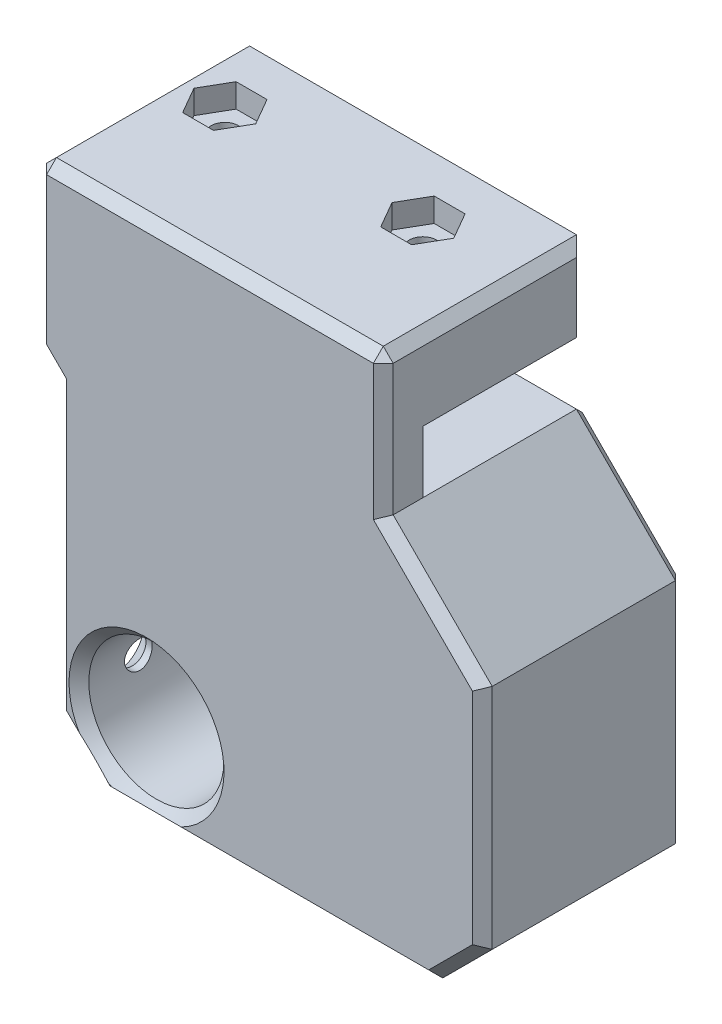
SolidWorks part; units mm, degrees
note: The reader was unsure of these and kept them because the rebuilt part matched: shared geometry of "스케치10<3>".
ref_plane "정면" through (0, 0, 0) normal (0, 0, 1) x (1, 0, 0)
ref_plane "윗면" through (0, 0, 0) normal (0, 1, 0) x (1, 0, 0)
ref_plane "우측면" through (0, 0, 0) normal (1, 0, 0) x (0, 0, -1)
sketch "스케치1" plane through (0, 0, 0) normal (0, 0, 1) x (1, 0, 0)
  line L0 (0, 0) -> (0, -2)
  line L1 (0, -2) -> (2, -4)
  line L2 (2, -4) -> (2, -33)
  line L3 (2, -33) -> (7, -38)
  line L4 (7, -38) -> (40, -38)
  line L5 (40, -38) -> (45, -33)
  line L6 (45, -33) -> (45, -10)
  line L7 (45, -10) -> (35, 0)
  line L8 (35, 0) -> (0, 0)
  dimension "D1" = 35
  dimension "D2" = 10
  dimension "D3" = 2
  dimension "D4" = 5
  dimension "D5" = 5
  dimension "D6" = 38
  dimension "D7" = 2
  dimension "D8" = 2
extrude "보스-돌출1" add sketch "스케치1" against normal blind 5
sketch "스케치2" plane through (0, 0, 0) normal (0, 0, 1) x (1, 0, 0)
  line L0 (0, -2) -> (0, 14.25)
  line L1 (0, 14.25) -> (35, 14.25)
  line L2 (35, 14.25) -> (35, -4)
  line L3 (35, -4) -> (2, -4)
  line L4 (2, -4) -> (0, -2)
  line L5 (0, 6.25) -> (35, 6.25) construction
  line L6 (35, 0) -> (0, 0) construction
  line L7 (2, -4) -> (2, -33) construction
  line L8 (7, -38) -> (40, -38) construction
  line L9 (45, -33) -> (45, -10) construction
  dimension "D1" = 6.25
  dimension "D2" = 8
extrude "보스-돌출2" add sketch "스케치2" along normal blind 4
sketch "스케치3" plane through (0, 0, 0) normal (0, 0, -1) x (-1, 0, 0)
  line L0 (-35, 0) -> (-35, 14.25) construction
  line L1 (0, 14.25) -> (-35, 14.25)
  line L2 (0, 14.25) -> (0, 6.25)
  line L3 (0, 6.25) -> (-35, 6.25)
  line L4 (-35, 14.25) -> (-35, 6.25)
  dimension "D1" = 8
sketch "스케치4" plane through (0, 0, 0) normal (0, 1, 0) x (1, 0, 0)
  line L2 (35, 0) -> (25, 0) construction
  line L3 (35, 0) -> (35, 10) construction
  line L4 (35, 10) -> (25, 10) construction
  line L5 (25, 0) -> (25, 10) construction
  dimension "D1" = 10
  dimension "D2" = 10
extrude "보스-돌출3" add sketch "스케치3" along normal blind 16.5 contours L3 L4 L1 L2
sketch "스케치5" plane through (0, 0, -5) normal (0, 0, -1) x (-1, 0, 0)
  line L0 (-35, -11.75) -> (-35, -38)
  line L1 (-35, -11.75) -> (-32, -8.75)
  line L2 (-2, -4) -> (0, -2)
  line L3 (-7, -38) -> (-40, -38) construction
  line L4 (-35, -38) -> (-40, -38)
  line L5 (-40, -38) -> (-45, -33)
  line L6 (-45, -33) -> (-45, -10)
  line L7 (-45, -10) -> (-35, 0)
  line L8 (-35, 0) -> (0, 0)
  line L9 (0, 0) -> (0, -2)
  line L10 (-2, -4) -> (-2, -8.75)
  line L11 (-2, -4) -> (-2, -33) construction
  line L12 (-2, -8.75) -> (-32, -8.75)
  line L15 (0, 14.25) -> (-35, 14.25) construction
  point P28 (-32.5508, -8.6209)
  dimension "D1" = 23
  dimension "D2" = 10
  dimension "D3" = 3
  dimension "D4" = 3
extrude "보스-돌출4" add sketch "스케치5" along normal blind 11.5
sketch "스케치6" plane through (0, 0, 0) normal (0, 1, 0) x (1, 0, 0)
  line L0 (5, 10) -> (25, 10) construction
  circle A0 centre (25, 10) radius 1.375
  circle A1 centre (5, 10) radius 1.375
  dimension "D2" = 2.75
  dimension "D3" = 2.75
  dimension "D1" = 20
extrude "컷-돌출1" cut sketch "스케치6" against normal through all both and the other way through all
sketch "스케치7" plane through (0, 14.25, 0) normal (0, 1, 0) x (1, 0, 0)
  line L1 (8.1177, 10) -> (6.5588, 12.7)
  line L2 (6.5588, 12.7) -> (3.4412, 12.7)
  line L3 (3.4412, 12.7) -> (1.8823, 10)
  line L4 (1.8823, 10) -> (3.4412, 7.3)
  line L5 (3.4412, 7.3) -> (6.5588, 7.3)
  line L6 (6.5588, 7.3) -> (8.1177, 10)
  line L7 (28.1177, 10) -> (26.5588, 12.7)
  line L8 (26.5588, 12.7) -> (23.4412, 12.7)
  line L9 (23.4412, 12.7) -> (21.8823, 10)
  line L10 (21.8823, 10) -> (23.4412, 7.3)
  line L11 (23.4412, 7.3) -> (26.5588, 7.3)
  line L12 (26.5588, 7.3) -> (28.1177, 10)
  circle A0 centre (5, 10) radius 2.7 construction
  circle A1 centre (25, 10) radius 2.7 construction
  dimension "D1" = 5.4
  dimension "D2" = 5.4
extrude "컷-돌출2" cut sketch "스케치7" against normal blind 2.4
sketch "스케치9" plane through (0, -8.75, 0) normal (0, -1, 0) x (1, 0, 0)
  circle A0 centre (5, -10) radius 2.7
  circle A1 centre (25, -10) radius 2.7
  dimension "D1" = 5.4
  dimension "D2" = 5.4
extrude "컷-돌출4" cut sketch "스케치9" against normal blind 3
sketch "스케치10" plane through (0, 0, -5) normal (0, 0, -1) x (-1, 0, 0)
  line L0 (-11.092, -30) -> (-27.592, -30) construction
  line L1 (-27.592, -22.8002) -> (-35, -22.8002)
  line L2 (-35, -38) -> (-35, -11.75) construction
  line L3 (-35, -22.8002) -> (-35, -38)
  line L4 (-7, -38) -> (-35, -38) construction
  line L5 (-20.3923, -31.5) -> (-20.3923, -38)
  line L6 (-20.3923, -38) -> (-35, -38)
  line L7 (-23.83, -28.5) -> (-20.5502, -28.5)
  line L8 (-23.83, -31.5) -> (-20.3923, -31.5)
  line L9 (-23.83, -31.5) -> (-23.83, -28.5)
  line L10 (-18.842, -30) -> (-18.842, -38)
  line L11 (-18.842, -38) -> (-7, -38)
  line L12 (-7, -38) -> (-2, -33)
  line L13 (-2, -33) -> (-2, -22.25)
  line L14 (-2, -8.75) -> (-2, -33) construction
  line L15 (-2, -22.25) -> (-11.092, -22.25)
  circle A0 centre (-11.092, -30) radius 4.5
  arc A1 (-23.83, -28.5) -> (-23.83, -31.5) centre (-27.592, -30) ccw
  arc A2 (-20.5502, -28.5) -> (-27.592, -22.8002) centre (-27.592, -30) ccw
  arc A3 (-11.092, -22.25) -> (-18.842, -30) centre (-11.092, -30) ccw
  point P19 (-23.83, -30)
  dimension "D1" = 8.1
  dimension "D3" = 9
  dimension "D6" = 15.5
  dimension "D2" = 16.5
  dimension "D4" = 8
  dimension "D5" = 3
extrude "보스-돌출5" add sketch "스케치10" along normal blind 5
extrude "보스-돌출6" add sketch "스케치10<3>" along normal blind 10
sketch "스케치10<3>" plane through (0, 0, -5) normal (0, 0, -1) x (-1, 0, 0) same geometry as "스케치10"
sketch "스케치13" plane through (0, 0, 0) normal (0, 0, 1) x (1, 0, 0)
  circle A0 centre (11.092, -30) radius 6.825
  dimension "D1" = 13.65
extrude "컷-돌출5" cut sketch "스케치13" against normal blind 8
sketch "스케치14" plane through (0, 0, -8) normal (0, 0, 1) x (1, 0, 0)
  circle A0 centre (11.092, -30) radius 6.025
  dimension "D1" = 12.05
extrude "컷-돌출6" cut sketch "스케치14" against normal blind 2.8
sketch "스케치15" plane through (2, 0, 0) normal (-1, 0, 0) x (0, 0, 1)
  line L0 (-10.8, -30) -> (2.5202, -30) construction
  line L1 (-10.8, -36.025) -> (-10.8, -23.975) construction
  line L2 (0, -4) -> (0, -33) construction
  circle A0 centre (-2, -30) radius 1.4
  dimension "D1" = 2.8
  dimension "D2" = 2
extrude "컷-돌출7" cut sketch "스케치15" against normal blind 12
chamfer "모따기2" distance 1 angle 45 2 edges at (31.642, -30, -10) (6.592, -30, -15)
sketch "스케치18" plane through (0, 0, 0) normal (0, 0, 1) x (1, 0, 0)
  line L8 (35, 0) -> (35, -4)
  line L9 (35, -4) -> (2, -4)
  line L10 (2, -4) -> (2, -33)
  line L11 (2, -33) -> (7, -38)
  line L12 (7, -38) -> (40, -38)
  line L13 (40, -38) -> (45, -33)
  line L14 (45, -33) -> (45, -10)
  line L15 (45, -10) -> (35, 0)
  line L16 (35, 0) -> (35, -4)
  line L17 (35, -4) -> (2, -4)
  line L18 (2, -4) -> (2, -33)
  line L19 (2, -33) -> (7, -38)
  line L20 (7, -38) -> (40, -38)
  line L21 (40, -38) -> (45, -33)
  line L22 (45, -33) -> (45, -10)
  line L23 (45, -10) -> (35, 0)
  circle A0 centre (11.092, -30) radius 6.825
  dimension "D2" = 13.65
  dimension "D1" = 0
extrude "보스-돌출9" add sketch "스케치18" along normal up to surface (4 mm away) up to face at (14.4, 3.7, 4)
sketch "스케치19" plane through (2, 0, 0) normal (-1, 0, 0) x (0, 0, 1)
  circle A0 centre (-2, -30) radius 2.825
  dimension "D1" = 5.65
extrude "컷-돌출9" cut sketch "스케치19" against normal blind 1.8 draft 41
chamfer "모따기4" distance 1 angle 45 26 edges at (12.921, -38, -15) (4.5, -35.5, -15) (2, -27.625, -15) (37.5, -38, -16.5) (42.5, -35.5, -16.5) (2, -6.375, -16.5) (1, -3, -16.5) (0, -1, -16.5) (17.5, 0, -16.5) (45, -21.5, -16.5) (40, -5, -16.5) (4.267, -30, 4) (35, 10.25, -16.5) (0, 10.25, -16.5) (1, -3, 4) (2, -18.5, 4) (4.5, -35.5, 4) (23.5, -38, 4) (42.5, -35.5, 4) (45, -21.5, 4) (40, -5, 4) (35, 14.25, -6.25) (35, 7.125, 4) (0, 14.25, -6.25) (0, 6.125, 4) (17.5, 14.25, 4)
